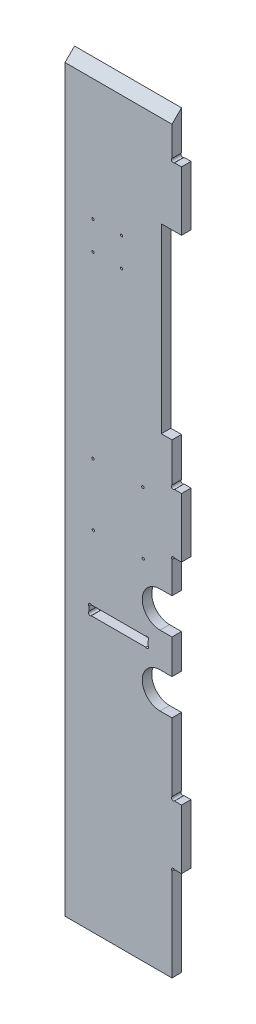
SolidWorks part; units mm, degrees
ref_plane "Plan de face" through (0, 0, 0) normal (0, 0, 1) x (1, 0, 0)
ref_plane "Plan de dessus" through (0, 0, 0) normal (0, 1, 0) x (1, 0, 0)
ref_plane "Plan de droite" through (0, 0, 0) normal (1, 0, 0) x (0, 0, -1)
sketch "Esquisse1" plane through (0, 0, 0) normal (0, 0, 1) x (1, 0, 0)
  line L1 (5.8799, 335.7035) -> (5.8799, 368.6564)
  line L2 (5.8799, 368.6564) -> (-3.1201, 368.6564)
  line L3 (5.8799, 596.7981) -> (5.8799, 255.0454) construction
  line L4 (-84.1201, 596.7981) -> (-84.1201, -23.4178)
  line L5 (-84.1201, -23.4178) -> (5.8799, -23.4178)
  line L6 (5.8799, 596.7981) -> (5.8799, 573.7035)
  line L7 (13.8799, 521.6564) -> (-3.1201, 521.6564)
  line L8 (13.8799, 521.6564) -> (13.8799, 571.5822)
  line L9 (13.8799, 571.5822) -> (8.0012, 571.5822)
  line L10 (-3.1201, 521.6564) -> (-3.1201, 368.6564)
  line L11 (-93.9802, 333.5822) -> (13.8799, 333.5822) construction
  line L13 (-84.1201, 206.5822) -> (5.8799, 206.5822) construction
  line L14 (-39.1201, -23.4178) -> (-39.1201, 596.7981) construction
  line L15 (-61.9988, 214.5822) -> (-16.2415, 214.5822)
  line L16 (8.0012, 333.5822) -> (13.8799, 333.5822)
  line L17 (13.8799, 333.5822) -> (13.8799, 283.5822)
  line L18 (13.8799, 283.5822) -> (8.0012, 283.5822)
  line L19 (5.8799, 281.4609) -> (5.8799, 255.0454)
  line L20 (47.6256, 56.5822) -> (-108.7526, 56.5822) construction
  line L21 (8.0012, 56.5822) -> (13.8799, 56.5822)
  line L22 (13.8799, 56.5822) -> (13.8799, 106.5822)
  line L23 (13.8799, 106.5822) -> (8.0012, 106.5822)
  line L24 (-64.1201, 212.4609) -> (-64.1201, 208.7035)
  line L25 (5.8799, 54.4609) -> (5.8799, -23.4178)
  line L26 (-61.9988, 206.5822) -> (-16.2415, 206.5822)
  line L27 (-14.1201, 212.4609) -> (-14.1201, 208.7035)
  line L28 (5.8799, 240.0454) -> (-84.1201, 240.0454) construction
  line L29 (-4.1201, 255.0454) -> (5.8799, 255.0454)
  line L30 (-4.1201, 225.0454) -> (5.8799, 225.0454)
  line L31 (5.8799, 225.0454) -> (5.8799, 196.1191)
  line L32 (5.8799, 240.0454) -> (5.8799, 196.1191) construction
  line L33 (37.7841, 606.6564) -> (-84.1201, 606.6564) construction
  line L34 (-84.1201, 596.7981) -> (-84.1201, 606.6564)
  line L35 (-84.1201, 606.6564) -> (5.8799, 606.6564)
  line L36 (5.8799, 606.6564) -> (5.8799, 596.7981)
  line L37 (-14.1201, 210.5822) -> (5.8799, 210.5822) construction
  line L38 (-4.1201, 196.1191) -> (5.8799, 196.1191)
  line L39 (-4.1201, 166.1191) -> (5.8799, 166.1191)
  line L40 (5.8799, 166.1191) -> (5.8799, 108.7035)
  line L41 (5.8799, 166.1191) -> (5.8799, -23.4178) construction
  line L42 (-150.2476, 495.7288) -> (-150.2476, 620.9623) construction
  line L44 (-81.1712, 486.4229) -> (-10.9246, 486.4229) construction
  line L54 (37.7841, -23.3436) -> (37.7841, 606.6564) construction
  arc A0 (5.8799, 573.7035) -> (8.0012, 571.5822) centre (6.9405, 572.6429) ccw
  arc A1 (5.8799, 335.7035) -> (8.0012, 333.5822) centre (6.9405, 334.6429) ccw
  arc A2 (8.0012, 283.5822) -> (5.8799, 281.4609) centre (6.9405, 282.5216) ccw
  arc A3 (5.8799, 108.7035) -> (8.0012, 106.5822) centre (6.9405, 107.6429) ccw
  arc A4 (8.0012, 56.5822) -> (5.8799, 54.4609) centre (6.9405, 55.5216) ccw
  arc A5 (-61.9988, 214.5822) -> (-64.1201, 212.4609) centre (-63.0595, 213.5216) ccw
  arc A6 (-14.1201, 212.4609) -> (-16.2415, 214.5822) centre (-15.1808, 213.5216) ccw
  arc A7 (-16.2415, 206.5822) -> (-14.1201, 208.7035) centre (-15.1808, 207.6429) ccw
  arc A8 (-64.1201, 208.7035) -> (-61.9988, 206.5822) centre (-63.0595, 207.6429) ccw
  arc A9 (-4.1201, 255.0454) -> (-4.1201, 225.0454) centre (-4.1201, 240.0454) ccw
  arc A10 (-4.1201, 166.1191) -> (-4.1201, 196.1191) centre (-4.1201, 181.1191) cw
  circle A11 centre (-60.5501, 496.3013) radius 1
  circle A12 centre (-36.5501, 496.3013) radius 1
  circle A13 centre (-60.5501, 472.3013) radius 1
  circle A14 centre (-36.5501, 472.3013) radius 1
  circle A15 centre (-60.5936, 321.7441) radius 1
  circle A16 centre (-18.5954, 321.9955) radius 1
  circle A17 centre (-18.2842, 269.9976) radius 1
  circle A18 centre (-60.2823, 269.7462) radius 1
  dimension "D2" = 8
  dimension "D3" = 80
  dimension "D5" = 307
  dimension "D7" = 1.5
  dimension "D8" = 8
  dimension "D9" = 8
  dimension "D10" = 230
  dimension "D11" = 90
  dimension "D12" = 20
  dimension "D13" = 20
  dimension "D14" = 8
  dimension "D15" = 125.2335
  dimension "D20" = 120.2335
  dimension "D21" = 630.0742
  dimension "D22" = 35.0742
  dimension "D4" = 357
  dimension "D6" = 1.5
  dimension "D23" = 49.9258
  dimension "D24" = 153
  dimension "D27" = 26.4155
extrude "Boss.-Extru.1" add sketch "Esquisse1" along normal blind 8
chamfer "Chanfrein1" distance 8 angle 45 1 edges at (-39.1201, 606.6564, 8)
